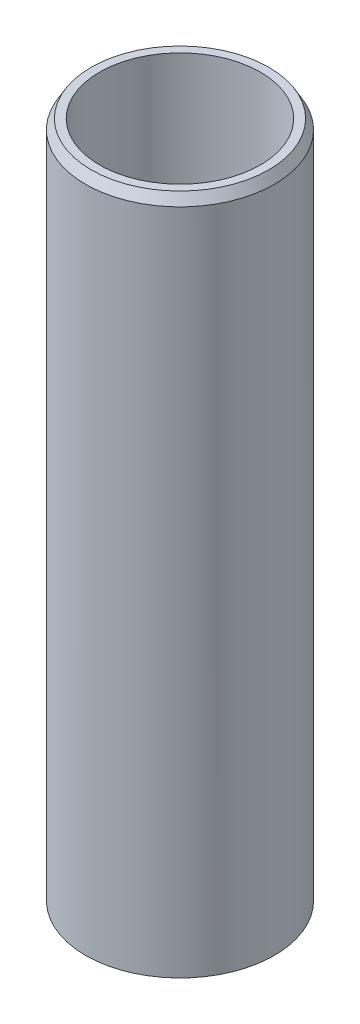
SolidWorks part; units mm, degrees
ref_plane "Front Plane" through (0, 0, 0) normal (0, 0, 1) x (1, 0, 0)
ref_plane "Top Plane" through (0, 0, 0) normal (0, 1, 0) x (1, 0, 0)
ref_plane "Right Plane" through (0, 0, 0) normal (1, 0, 0) x (0, 0, -1)
sketch "Sketch1" plane through (0, 0, 0) normal (0, 1, 0) x (1, 0, 0)
  circle A0 centre (0, 0) radius 42.5
  dimension "SHAFT_OD" = 85
extrude "Boss-Extrude1" add sketch "Sketch1" along normal blind 307.3594
sketch "Sketch2" plane through (0, 0, 0) normal (0, 1, 0) x (1, 0, 0)
  circle A0 centre (0, 0) radius 36.1984
  dimension "BORE_D" = 72.3967
extrude "Cut-Extrude1" cut sketch "Sketch2" along normal through all
chamfer "Chamfer1" distance 4.3805 angle 30 2 edges at (0, 307.3594, 42.5) (0, 0, 42.5) first distance on face at (0, 307.3594, 42.5) first distance on face at (0, 0, 36.1984)
